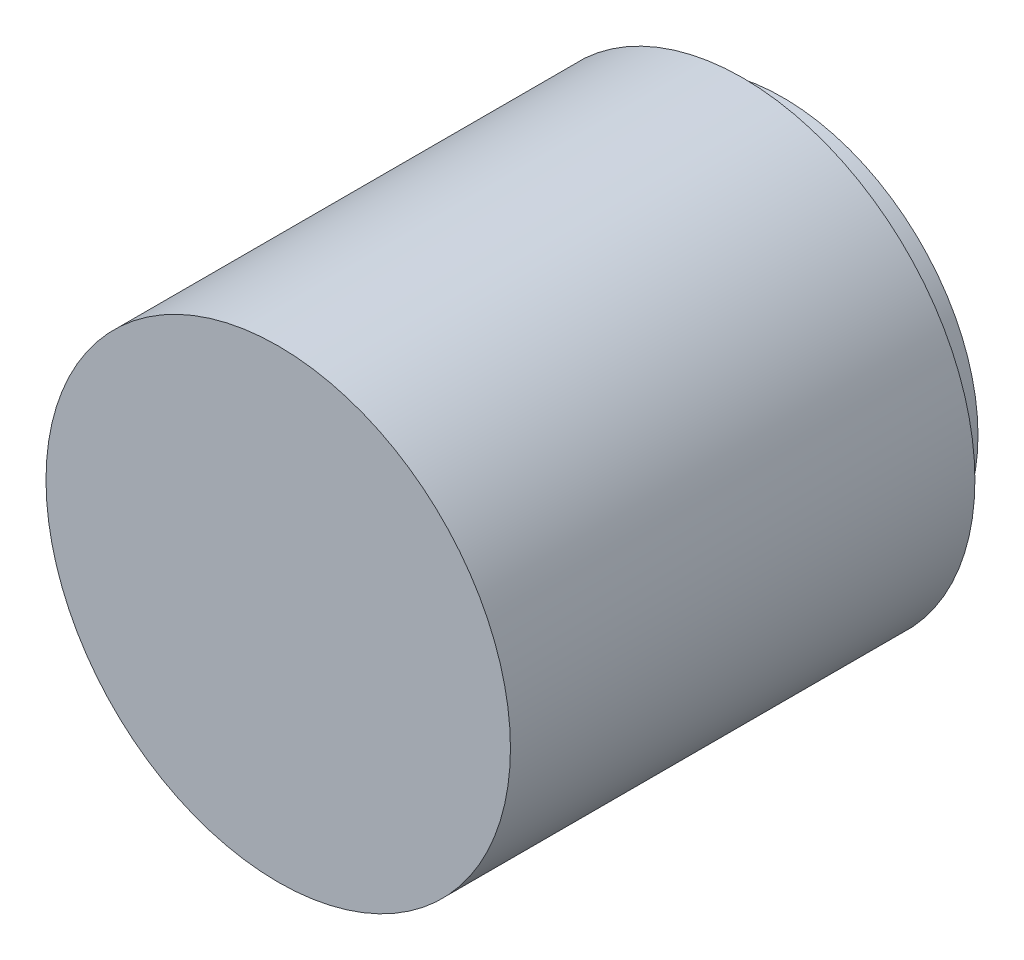
SolidWorks part; units mm, degrees
ref_plane "Front Plane" through (0, 0, 0) normal (0, 0, 1) x (1, 0, 0)
ref_plane "Top Plane" through (0, 0, 0) normal (0, 1, 0) x (1, 0, 0)
ref_plane "Right Plane" through (0, 0, 0) normal (1, 0, 0) x (0, 0, -1)
sketch "Sketch1" plane through (0, 0, 0) normal (0, 0, 1) x (1, 0, 0)
  circle A0 centre (0, 0) radius 37.5
  dimension "D1" = 75
extrude "Boss-Extrude1" add sketch "Sketch1" along normal blind 75
sketch "Sketch2" plane through (0, 0, 0) normal (0, 0, -1) x (-1, 0, 0)
  circle A0 centre (0, 0) radius 31.5
  dimension "D1" = 63
extrude "Boss-Extrude2" add sketch "Sketch2" along normal blind 6.5
sketch "Sketch3" plane through (0, 0, -6.5) normal (0, 0, -1) x (-1, 0, 0)
  circle A0 centre (0, 0) radius 15.75
  dimension "D1" = 31.5
extrude "Cut-Extrude1" cut sketch "Sketch3" against normal blind 6.5
sketch "Sketch4" plane through (0, 0, -6.5) normal (0, 0, -1) x (-1, 0, 0)
  circle A0 centre (25, 0) radius 3
  circle A1 centre (0, -25) radius 3
  circle A2 centre (-25, 0) radius 3
  circle A3 centre (0, 25) radius 3
  circle A4 centre (0, 0) radius 25
  point P11 (25, 0)
  point P12 (0, -25)
  point P13 (-25, 0)
  point P14 (0, 25)
  dimension "D1" = 50
extrude "Cut-Extrude2" cut sketch "Sketch4" against normal blind 5 contours A0 A4 | A4 A3 | A3 A4 | A0 | A2 | A1 region at (-23.6949, 0, -6.5) region at (0, 26.2403, -6.5) region at (0, 23.6949, -6.5)
